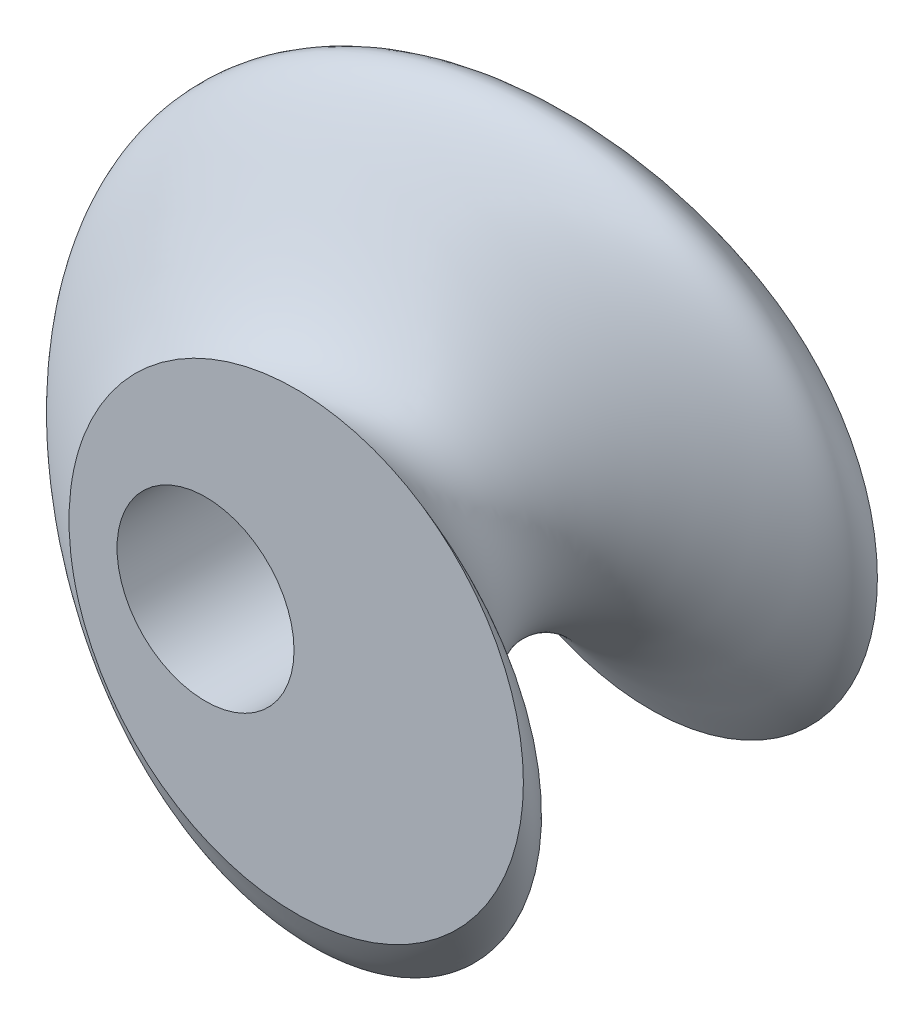
SolidWorks part; units mm, degrees
ref_plane "Ebene vorne" through (0, 0, 0) normal (0, 0, 1) x (1, 0, 0)
ref_plane "Ebene oben" through (0, 0, 0) normal (0, 1, 0) x (1, 0, 0)
ref_plane "Ebene rechts" through (0, 0, 0) normal (1, 0, 0) x (0, 0, -1)
sketch "Skizze1" plane through (0, 0, 0) normal (0, 0, 1) x (1, 0, 0)
  circle A0 centre (0, 0) radius 6.4173
  dimension "D1" = 12.8346
ref_plane "Ebene1" through (0, 0, 0) normal (0, 0, 1) x (1, 0, 0)
sketch "Skizze3" plane through (0, 0, 0) normal (0, 0, 1) x (1, 0, 0)
  point P0 (-2.5613, 0)
  dimension "D1" = 2.5613
ref_axis "Achse1" through (-2.5613, 0, -26.4244) along (0, 0, 1)
sketch "Skizze4" plane through (0, 0, 0) normal (0, 0, 1) x (1, 0, 0)
  circle A0 centre (-2.5613, 0) radius 3.5934
curve "Spirale/Helix2" pitch 10 height 10 radius 3.5934 centre (-2.5613, 0, 0) axis (0, 0, 1) start towards (1, 0, 0)
sweep "Austragung1" add profiles "Skizze1" path "Spirale/Helix2"
sketch "Skizze5" plane through (0, 0, 10) normal (0, 0, 1) x (1, 0, 0)
  circle A0 centre (-2.5613, 0) radius 2.5
extrude "Schnitt-Linear austragen1" cut sketch "Skizze5" against normal blind 10
